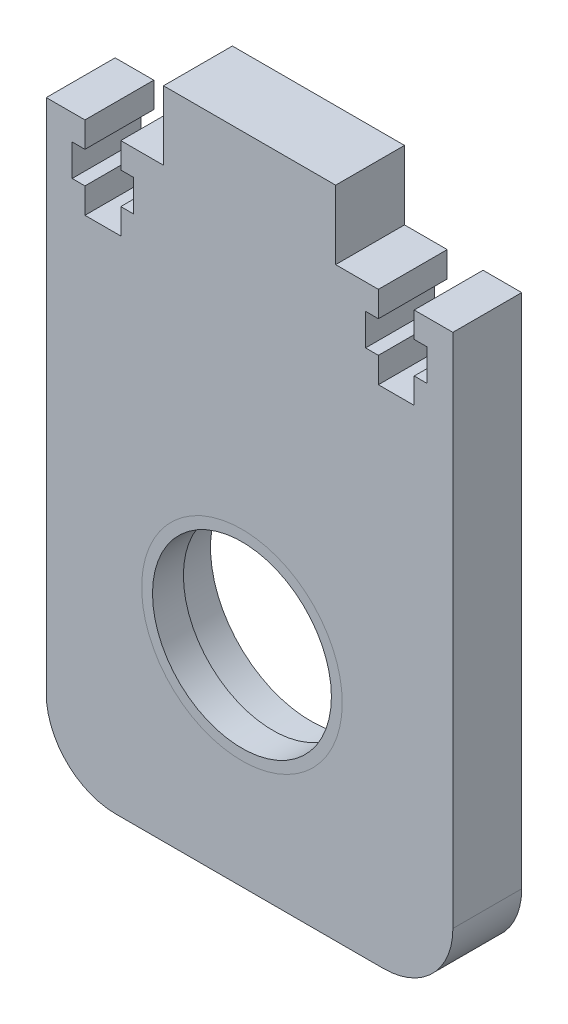
SolidWorks part; units mm, degrees
ref_plane "Front Plane" through (0, 0, 0) normal (0, 0, 1) x (1, 0, 0)
ref_plane "Top Plane" through (0, 0, 0) normal (0, 1, 0) x (1, 0, 0)
ref_plane "Right Plane" through (0, 0, 0) normal (1, 0, 0) x (0, 0, -1)
sketch "Sketch12" plane through (0, 0, 0) normal (0, 0, 1) x (1, 0, 0)
  line L0 (62.1258, 0) -> (62.1258, 108.03)
  line L1 (62.1258, 108.03) -> (137.1258, 108.03)
  line L2 (62.1258, 0) -> (137.1258, 0)
  line L3 (137.1258, 108.03) -> (137.1258, 0)
  circle A0 centre (99.6258, 37.5) radius 25.4
  circle A1 centre (99.6258, 37.5) radius 6.5
  dimension "D3" = 50.8
  dimension "D4" = 13
  dimension "D1" = 108.03
  dimension "D2" = 75
extrude "Boss-Extrude10" add sketch "Sketch12" along normal blind 12.7 separate body contours L1 L3 L2 L0
sketch "Sketch15" plane through (0, 0, 12.7) normal (0, 0, 1) x (1, 0, 0)
  circle A0 centre (98.2196, 38.6276) radius 25.4
  dimension "D1" = 50.8
sketch "Sketch24" plane through (0, 0, 12.7) normal (0, 0, 1) x (1, 0, 0)
  line L0 (62.1258, 108.03) -> (62.1258, 104.03)
  line L1 (62.1258, 0) -> (62.1258, 108.03) construction
  line L2 (62.1258, 104.03) -> (137.1258, 104.03)
  line L3 (137.1258, 108.03) -> (137.1258, 0) construction
  line L4 (137.1258, 104.03) -> (137.1258, 108.03)
  line L5 (137.1258, 108.03) -> (62.1258, 108.03)
  dimension "D1" = 4
sketch "Sketch25" plane through (0, 0, 12.7) normal (0, 0, 1) x (1, 0, 0)
  circle A0 centre (98.2196, 38.6276) radius 18.5
  dimension "D1" = 37
extrude "Cut-Extrude1" cut sketch "Sketch25" against normal through all
sketch "Sketch26" plane through (0, 0, 12.7) normal (0, 0, 1) x (1, 0, 0)
  circle A0 centre (98.2196, 38.6276) radius 16.5
  circle A1 centre (98.2196, 38.6276) radius 18.5
  dimension "D1" = 37
  dimension "D2" = 2
extrude "Boss-Extrude15" add sketch "Sketch26" against normal blind 5.7 separate body
fillet "Fillet1" radius 12.8 2 edges at (137.1258, 0, 6.35) (62.1258, 0, 6.35)
sketch "Sketch27" plane through (0, 0, 0) normal (0, 0, -1) x (-1, 0, 0)
  line L0 (-69.2616, 108.03) -> (-69.2616, 103.331)
  line L1 (-137.1258, 108.03) -> (-62.1258, 108.03) construction
  line L2 (-69.2616, 103.331) -> (-66.8996, 103.331)
  line L3 (-66.8996, 103.331) -> (-66.8996, 97.489)
  line L4 (-66.8996, 97.489) -> (-69.2616, 97.489)
  line L5 (-69.2616, 97.489) -> (-69.2616, 92.79)
  line L6 (-69.2616, 92.79) -> (-75.8656, 92.79)
  line L7 (-75.8656, 92.79) -> (-75.8656, 97.489)
  line L8 (-75.8656, 97.489) -> (-78.2276, 97.489)
  line L9 (-78.2276, 97.489) -> (-78.2276, 103.331)
  line L10 (-78.2276, 103.331) -> (-75.8656, 103.331)
  line L11 (-75.8656, 103.331) -> (-75.8656, 108.03)
  line L12 (-75.8656, 108.03) -> (-69.2616, 108.03)
  line L13 (-123.3861, 103.331) -> (-123.3861, 108.03)
  line L15 (-99.6258, 108.03) -> (-99.6258, 67.3255)
  line L28 (-121.0241, 103.331) -> (-123.3861, 103.331)
  line L29 (-121.0241, 97.489) -> (-121.0241, 103.331)
  line L30 (-123.3861, 97.489) -> (-121.0241, 97.489)
  line L31 (-123.3861, 92.79) -> (-123.3861, 97.489)
  line L32 (-129.9901, 92.79) -> (-123.3861, 92.79)
  line L33 (-129.9901, 97.489) -> (-129.9901, 92.79)
  line L34 (-132.3521, 97.489) -> (-129.9901, 97.489)
  line L35 (-132.3521, 103.331) -> (-132.3521, 97.489)
  line L36 (-129.9901, 103.331) -> (-132.3521, 103.331)
  line L37 (-129.9901, 108.03) -> (-129.9901, 103.331)
  line L38 (-123.3861, 108.03) -> (-129.9901, 108.03)
  line M19 (-62.1258, 108.03) -> (-137.1258, 108.03)
  dimension "D1" = 6.604
  dimension "D2" = 11.328
  dimension "D3" = 5.842
  dimension "D4" = 15.24
ref_axis "Axis2" through (99.6258, 108.03, 0) along (0, -1, 0)
extrude "Cut-Extrude2" cut sketch "Sketch27" against normal through all contours L11 L10 L9 L8 L7 L6 L5 L4 L3 L2 L0 M19 | L37 L36 L35 L34 L33 L32 L31 L30 L29 L28 L13 M19 region at (126.6881, 100.41, 0) region at (72.5636, 100.41, 0)
sketch "Sketch28" plane through (0, 108.03, 0) normal (0, 1, 0) x (1, 0, 0)
  line L0 (99.6258, 0) -> (83.7508, 0)
  line L1 (75.8656, 0) -> (123.3861, 0) construction
  line L2 (83.7508, 0) -> (83.7508, -12.7)
  line L3 (72.8196, -12.7) -> (123.6196, -12.7) construction
  line L4 (83.7508, -12.7) -> (115.5008, -12.7)
  line L5 (115.5008, -12.7) -> (115.5008, 0)
  line L6 (115.5008, 0) -> (99.6258, 0)
  dimension "D1" = 31.75
extrude "Boss-Extrude16" add sketch "Sketch28" along normal blind 12.7
